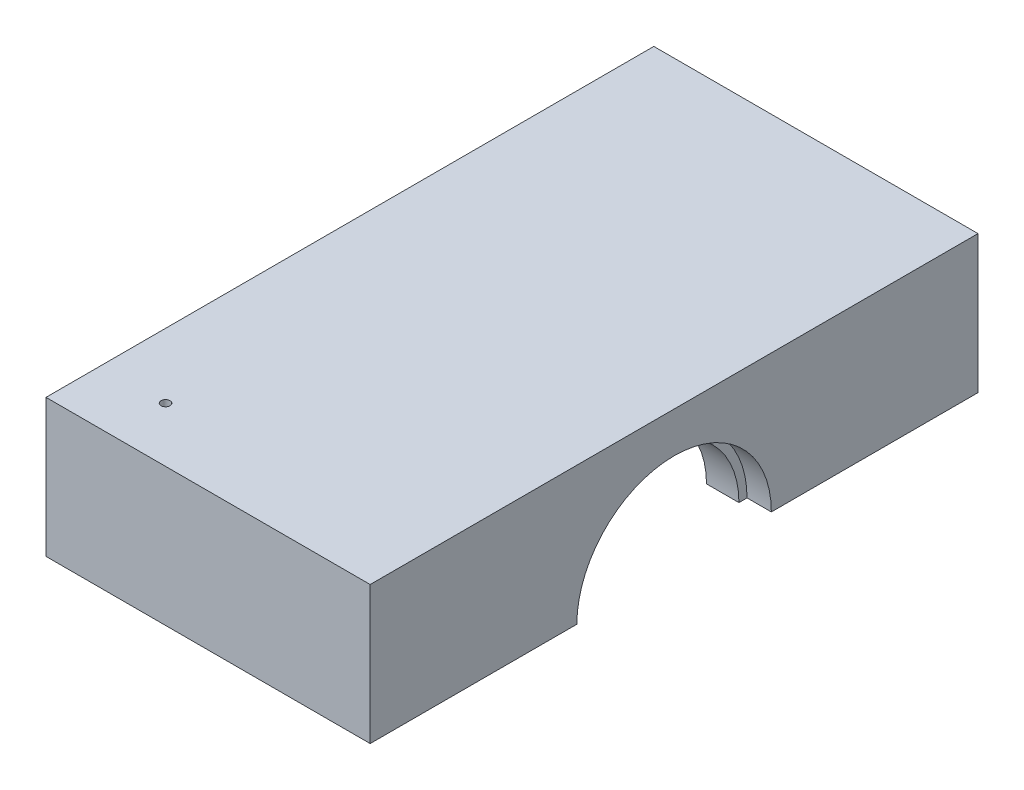
SolidWorks part; units mm, degrees
ref_plane "Спереди" through (0, 0, 0) normal (0, 0, 1) x (1, 0, 0)
ref_plane "Сверху" through (0, 0, 0) normal (0, 1, 0) x (1, 0, 0)
ref_plane "Справа" through (0, 0, 0) normal (1, 0, 0) x (0, 0, -1)
sketch "Эскиз1" plane through (0, 0, 0) normal (1, 0, 0) x (0, 0, -1)
  line L0 (-72.0575, 0) -> (82.2, 0) construction
  line L1 (0, 49.5774) -> (0, -46.7011) construction
  line L2 (-75, 24) -> (-75, 34)
  line L3 (75, 24) -> (-75, 24)
  line L4 (-75, 34) -> (75, 34)
  line L5 (75, 34) -> (75, 24)
  dimension "D1" = 75
  dimension "D2" = 150
  dimension "D3" = 75
  dimension "D4" = 10
extrude "Бобышка-Вытянуть2" add sketch "Эскиз1" along normal blind 40 and the other way blind 40
sketch "Эскиз2" plane through (40, 0, 0) normal (1, 0, 0) x (0, 0, -1)
  line L0 (-26, 0) -> (-22, 0)
  line L1 (22, 0) -> (26, 0)
  arc A0 (-22, 0) -> (22, 0) centre (0, 0) cw
  arc A1 (-26, 0) -> (26, 0) centre (0, 0) cw
  dimension "D1" = 22
  dimension "D2" = 26
extrude "Бобышка-Вытянуть3" add sketch "Эскиз2" against normal blind 14 separate body
sketch "Эскиз3" plane through (-40, 0, 0) normal (-1, 0, 0) x (0, 0, 1)
  line L0 (26, 0) -> (22, 0) construction
  line L1 (-26, 0) -> (-22, 0)
  line L2 (22, 0) -> (26, 0)
  arc A0 (-22, 0) -> (22, 0) centre (0, 0) cw
  arc A1 (22, 0) -> (-22, 0) centre (0, 0) ccw construction
  arc A2 (-26, 0) -> (26, 0) centre (0, 0) cw
  dimension "D1" = 26
  dimension "D2" = 22
  dimension "D3" = 4
  dimension "D4" = 4
extrude "Бобышка-Вытянуть4" add sketch "Эскиз3" against normal blind 14
sketch "Эскиз4" plane through (0, 24, 0) normal (0, -1, 0) x (-1, 0, 0)
  line L0 (26, 26) -> (40, 26) construction
  line L1 (40, -26) -> (38, -26)
  line L2 (40, -26) -> (40, 26)
  line L3 (40, 26) -> (38, 26)
  line L4 (38, -26) -> (38, 26)
  line L5 (-26, 26) -> (-40, 26) construction
  line L6 (-40, -26) -> (-38, -26)
  line L7 (-40, -26) -> (-40, 26)
  line L8 (-40, 26) -> (-38, 26)
  line L9 (-38, -26) -> (-38, 26)
  dimension "D1" = 2
  dimension "D2" = 2
extrude "Бобышка-Вытянуть5" add sketch "Эскиз4" along normal blind 24
sketch "Эскиз5" plane through (40, 0, 0) normal (1, 0, 0) x (0, 0, -1)
  line L0 (-26, 0) -> (26, 0) construction
  circle A0 centre (0, 0) radius 22
  dimension "D1" = 44
extrude "Вырез-Вытянуть1" cut sketch "Эскиз5" against normal blind 81
sketch "Эскиз6" plane through (0, 24, 0) normal (0, -1, 0) x (-1, 0, 0)
  line L0 (38, 28) -> (36, 28)
  line L1 (38, -73) -> (-38, -73)
  line L2 (38, -73) -> (38, -28)
  line L3 (-36, 28) -> (-38, 28)
  line L4 (-38, -73) -> (-38, -27.9991)
  line L5 (-38, -27.9991) -> (-36, -27.9991)
  line L6 (38, 28) -> (38, 73)
  line L7 (38, 73) -> (-38, 73)
  line L8 (-38, 28) -> (-38, 73)
  line L9 (36, -28) -> (38, -28)
  line L10 (36, -28) -> (36, -13)
  line L11 (40, -75) -> (40, -26) construction
  line L13 (-40, -75) -> (-40, -26) construction
  line L14 (-40, 26) -> (-40, 75) construction
  line L15 (40, 26) -> (40, 75) construction
  line L16 (40, 75) -> (-40, 75) construction
  line L18 (-40, -26) -> (-38, -26) construction
  line L19 (-38, 26) -> (-40, 26) construction
  line L20 (36, 13) -> (36, 28)
  line L21 (40, 26) -> (38, 26) construction
  line L22 (38, -26) -> (40, -26) construction
  line L23 (24, -13) -> (24, 13)
  line L24 (36, -13) -> (24, -13)
  line L25 (-36, 28) -> (-36, 13)
  line L26 (36, 13) -> (24, 13)
  line L27 (-36, -13) -> (-36, -27.9991)
  line L28 (-24, 13) -> (-36, 13)
  line L29 (-36, -13) -> (-24, -13)
  line L30 (-24, -13) -> (-24, 13)
  dimension "D1" = 2
  dimension "D2" = 2
  dimension "D3" = 2
  dimension "D4" = 2
  dimension "D5" = 2
  dimension "D6" = 2
  dimension "D7" = 1.9991
  dimension "D8" = 2
  dimension "D9" = 2
  dimension "D10" = 2
  dimension "D11" = 2
  dimension "D12" = 2
  dimension "D16" = 2
  dimension "D17" = 26
  dimension "D22" = 2
  dimension "D25" = 12
extrude "Вырез-Вытянуть6" cut sketch "Эскиз6" against normal blind 8
sketch "Эскиз7" plane through (0, 32, 0) normal (0, -1, 0) x (1, 0, 0)
  line L1 (-27.5, 65) -> (38, 65)
  line L2 (-27.5, 65) -> (-27.5, 13)
  line L3 (-27.5, 13) -> (38, 13)
  line L4 (38, 65) -> (38, 13)
  line L5 (-29, 66.5) -> (40, 66.5)
  line L6 (-29, 66.5) -> (-29, 11.5)
  line L7 (-29, 11.5) -> (40, 11.5)
  line L8 (40, 66.5) -> (40, 11.5)
  line L9 (24, 13) -> (36, 13) construction
  line L10 (38, 27.9991) -> (38, 73) construction
  dimension "D1" = 52
  dimension "D2" = 65.5
  dimension "D3" = 1.5
  dimension "D4" = 2
  dimension "D5" = 1.5
  dimension "D6" = 1.5
  dimension "D7" = 0
  dimension "D8" = 0
extrude "Бобышка-Вытянуть6" add sketch "Эскиз7" along normal blind 4
sketch "Эскиз12" plane through (0, 0, 13) normal (0, 0, 1) x (1, 0, 0)
  line L0 (-40, 34) -> (-40, 24) construction
  line L1 (-28, 28.0383) -> (38, 28.0383)
  line L2 (-28, 28.0383) -> (-28, 29.5383)
  line L3 (-28, 29.5383) -> (38, 29.5383)
  line L4 (38, 28.0383) -> (38, 29.5383)
  line L6 (40, 34) -> (40, 24) construction
  dimension "D1" = 12
  dimension "D2" = 2
  dimension "D3" = 1.5
extrude "Бобышка-Вытянуть8" add sketch "Эскиз12" along normal blind 5
sketch "Эскиз13" plane through (40, 0, 0) normal (1, 0, 0) x (0, 0, -1)
  line L0 (22, 0) -> (26, 0) construction
  line L1 (-26, 0) -> (-22, 0) construction
  line L2 (-24, 0) -> (-22, 0)
  line L3 (24, 0) -> (22, 0)
  arc A0 (-22, 0) -> (22, 0) centre (0, 0) cw
  arc A1 (-24, 0) -> (24, 0) centre (0, 0) cw
  dimension "D1" = 22
  dimension "D2" = 24
extrude "Вырез-Вытянуть7" cut sketch "Эскиз13" against normal blind 6
sketch "Эскиз14" plane through (-40, 0, 0) normal (-1, 0, 0) x (0, 0, 1)
  line L0 (22, 0) -> (26, 0) construction
  line L2 (-24, 0) -> (-22, 0)
  line L3 (22, 0) -> (24, 0)
  arc A0 (-22, 0) -> (22, 0) centre (0, 0) cw
  arc A1 (24, 0) -> (-24, 0) centre (0, 0) ccw
  dimension "D1" = 22
  dimension "D2" = 24
extrude "Вырез-Вытянуть8" cut sketch "Эскиз14" against normal blind 6
sketch "Эскиз15" plane through (0, 32, 0) normal (0, -1, 0) x (1, 0, 0)
  line L1 (38, 65) -> (-27.5, 65) construction
  line L2 (-27.5, 65) -> (-27.5, 13) construction
  circle A0 centre (-24, 61.5) radius 1.1
  dimension "D1" = 2.2
  dimension "D2" = 3.5
  dimension "D3" = 3.5
extrude "Вырез-Вытянуть9" cut sketch "Эскиз15" against normal blind 4
sketch "Эскиз16" plane through (0, 32, 0) normal (0, -1, 0) x (1, 0, 0)
  line L0 (38, 27.9991) -> (38, 73) construction
  line L1 (38, 31.5475) -> (22.7538, 31.5475)
  line L2 (38, 31.5475) -> (38, 13)
  line L3 (38, 13) -> (22.7538, 13)
  line L4 (22.7538, 31.5475) -> (22.7538, 13)
  line L5 (-24, 13) -> (24, 13) construction
extrude "Вырез-Вытянуть10" cut sketch "Эскиз16" along normal blind 2
sketch "Эскиз17" plane through (0, 24, 0) normal (0, -1, 0) x (1, 0, 0)
  line L0 (38, 13) -> (38, 65) construction
  line L1 (38, 30.6575) -> (24.2096, 30.6575)
  line L2 (38, 30.6575) -> (38, 18)
  line L3 (38, 18) -> (24.2096, 18)
  line L4 (24.2096, 30.6575) -> (24.2096, 18)
  line L5 (-27.5, 18) -> (36, 18) construction
extrude "Вырез-Вытянуть11" cut sketch "Эскиз17" against normal blind 8
sketch "Эскиз18" plane through (0, 24, 0) normal (0, -1, 0) x (1, 0, 0)
  line L0 (-40, -24) -> (-38, -24)
  line L1 (-40, 75) -> (40, 75)
  line L2 (-40, 75) -> (-40, 26)
  line L3 (-34, -24) -> (-40, -24) construction
  line L4 (40, 75) -> (40, 26)
  line L5 (-38, 73) -> (38, 73)
  line L6 (-38, 73) -> (-38, 26)
  line L7 (-38, -24) -> (-38, -26)
  line L8 (38, 73) -> (38, 26)
  line L9 (38, -26) -> (38, -24)
  line L10 (-40, -24) -> (-40, -75)
  line L11 (-40, -75) -> (40, -75)
  line L12 (40, -24) -> (40, -75)
  line L13 (34, -24) -> (40, -24) construction
  line L14 (-38, -26) -> (-38, -73)
  line L15 (-38, -73) -> (38, -73)
  line L16 (38, -26) -> (38, -73)
  line L17 (38, -24) -> (40, -24)
  line L18 (-40, 26) -> (-40, 24)
  line L19 (-40, 24) -> (-38, 24)
  line L20 (-34, 24) -> (-40, 24) construction
  line L21 (-38, 24) -> (-38, 26)
  line L22 (40, 26) -> (40, 24)
  line L23 (40, 24) -> (38, 24)
  line L24 (34, 24) -> (40, 24) construction
  line L25 (38, 24) -> (38, 26)
extrude "Бобышка-Вытянуть9" add sketch "Эскиз18" along normal blind 24
